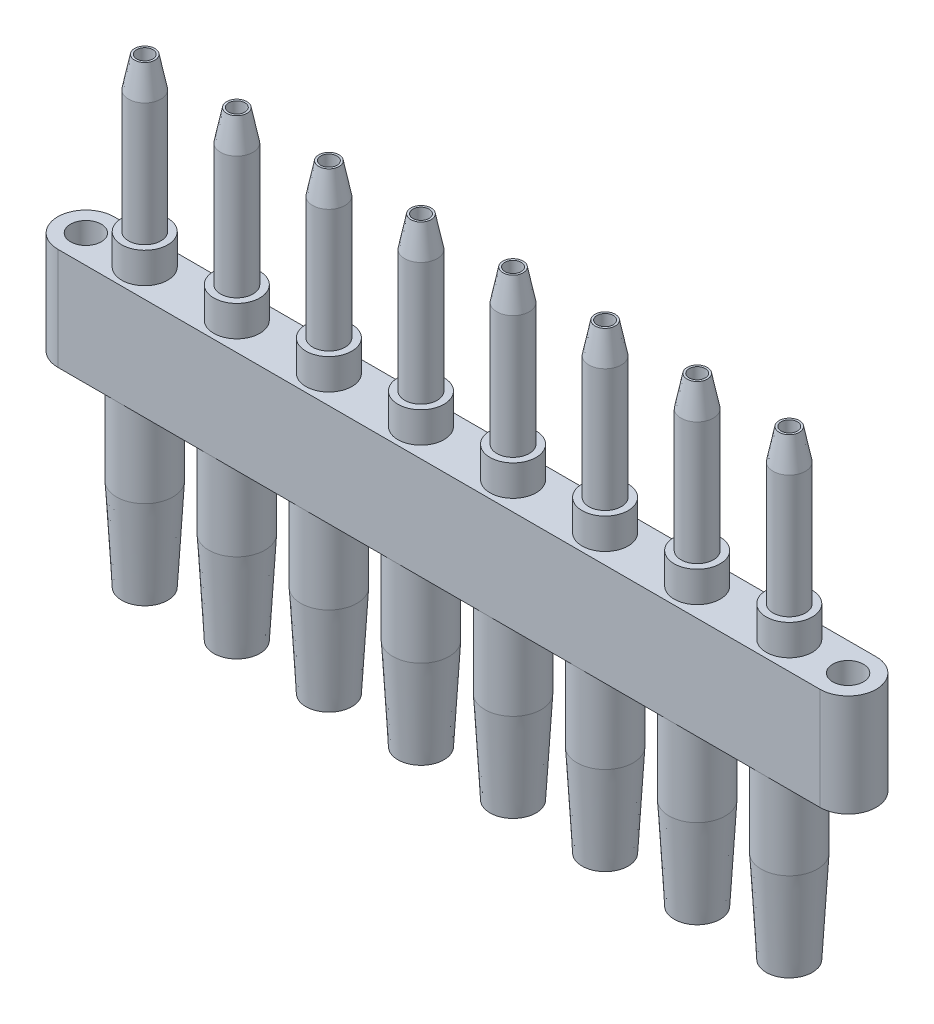
SolidWorks part; units mm, degrees
ref_plane "Front Plane" through (0, 0, 0) normal (0, 0, 1) x (1, 0, 0)
ref_plane "Top Plane" through (0, 0, 0) normal (0, 1, 0) x (1, 0, 0)
ref_plane "Right Plane" through (0, 0, 0) normal (1, 0, 0) x (0, 0, -1)
sketch "Sketch1" plane through (0, 0, 0) normal (0, 1, 0) x (1, 0, 0)
  line L0 (0, 0) -> (0, 22.2718) construction
  circle A0 centre (0, 0) radius 4.5 construction
  circle A1 centre (-4.5, 0) radius 2.75
  circle A2 centre (4.5, 0) radius 2.75
  circle A3 centre (13.5, 0) radius 2.75
  circle A4 centre (22.5, 0) radius 2.75
  circle A5 centre (31.5, 0) radius 2.75
  circle A6 centre (-13.5, 0) radius 2.75
  circle A7 centre (-22.5, 0) radius 2.75
  circle A8 centre (-31.5, 0) radius 2.75
  circle A11 centre (-31.5, 0) radius 0.7937
  circle A12 centre (-22.5, 0) radius 0.7937
  circle A13 centre (-13.5, 0) radius 0.7937
  circle A14 centre (-4.5, 0) radius 0.7937
  circle A15 centre (4.5, 0) radius 0.7937
  circle A16 centre (13.5, 0) radius 0.7937
  circle A17 centre (22.5, 0) radius 0.7937
  circle A18 centre (31.5, 0) radius 0.7937
  dimension "D5" = 5.5
  dimension "D6" = 8
  dimension "D7" = 1.5875
  dimension "D8" = 9
  dimension "D4" = 4
extrude "Boss-Extrude1" add sketch "Sketch1" against normal blind 8.1
ref_plane "Plane1" through (0, -8.1, 0) normal (0, -1, 0) x (1, 0, 0)
ref_axis "Axis2" through (-31.5, -8.1, 0) along (0, 1, 0)
sketch "Sketch7" plane through (0, 0, 0) normal (0, 0, 1) x (1, 0, 0)
  line L1 (-31.5, -11) -> (-31.5, -15.2529)
sketch "Sketch8" plane through (0, -8.1, 0) normal (0, -1, 0) x (1, 0, 0)
  line L0 (-31.5, 0.7938) -> (-31.5, 2.75)
  circle A0 centre (-31.5, 0) radius 0.7937 construction
  circle A1 centre (-31.5, 0) radius 2.75 construction
ref_plane "Plane2" through (-31.5, 0, 0) normal (1, 0, 0) x (0, 0, -1)
sketch "Sketch9" plane through (-31.5, 0, 0) normal (1, 0, 0) x (0, 0, -1)
  line L0 (0, -11) -> (0, -15.2529) construction
  line L1 (-6.8585, -8.1) -> (6.8585, -8.1) construction
  line L2 (-0.7938, -8.1) -> (-0.7937, -17.1)
  line L3 (-0.7938, -8.1) -> (-2.75, -8.1)
  line L4 (0, -15.2529) -> (0, -21) construction
  line L5 (-0.7937, -17.1) -> (-2.25, -17.1)
  line L6 (-2.75, -8.1) -> (-2.25, -17.1)
  circle A0 centre (0, -8.1) radius 0.7937 construction
  circle A1 centre (0, -8.1) radius 1.5875 construction
  circle A2 centre (0, -17.1) radius 2.25 construction
  circle A3 centre (0, -8.1) radius 2.75 construction
  dimension "D1" = 4.5
  dimension "D2" = 5.5
  dimension "D3" = 9
revolve "Revolve1" add sketch "Sketch9" angle 360 about L4
ref_axis "Axis3" through (45.6173, -8.1, 0) along (-1, 0, 0)
pattern_linear "LPattern4" count 8 spacing 9 along (1, 0, 0) of bodies 109
sketch "Sketch10" plane through (0, 0, 0) normal (0, 1, 0) x (1, 0, 0)
  line L0 (0, 0) -> (-8.0623, 0) construction
  line L1 (-37.25, 2.75) -> (-37.25, -2.75) construction
  line L2 (0, 0) -> (0, 13.1499) construction
  line L3 (-37.25, 0) -> (-40, 0) construction
  line L4 (37.25, -2.75) -> (-37.25, -2.75)
  line L5 (37.25, 2.75) -> (-37.25, 2.75)
  line L6 (37.25, 2.75) -> (37.25, -2.75) construction
  line L7 (37.25, 0) -> (40, 0) construction
  line L9 (45.6173, 0) -> (-45.6488, 0) construction
  circle A0 centre (-31.5, 0) radius 0.7937
  circle A1 centre (-22.5, 0) radius 0.7937
  arc A2 (-37.25, 2.75) -> (-37.25, -2.75) centre (-37.25, 0) ccw
  circle A3 centre (-37.25, 0) radius 1.5
  circle A4 centre (37.25, 0) radius 1.5
  arc A5 (37.25, 2.75) -> (37.25, -2.75) centre (37.25, 0) cw
  circle A8 centre (-22.5, 0) radius 2.75 construction
  circle A9 centre (-13.5, 0) radius 0.7937
  circle A10 centre (-13.5, 0) radius 2.75 construction
  circle A11 centre (-4.5, 0) radius 0.7937
  circle A12 centre (-4.5, 0) radius 2.75 construction
  circle A13 centre (4.5, 0) radius 0.7937
  circle A14 centre (-31.5, 0) radius 2.75 construction
  circle A15 centre (4.5, 0) radius 2.75 construction
  circle A16 centre (13.5, 0) radius 0.7937
  circle A17 centre (13.5, 0) radius 2.75 construction
  circle A18 centre (22.5, 0) radius 0.7937
  circle A19 centre (22.5, 0) radius 2.75 construction
  circle A20 centre (31.5, 0) radius 0.7937
  circle A21 centre (31.5, 0) radius 2.75 construction
  dimension "D1" = 8
  dimension "D2" = 3
extrude "Boss-Extrude2" add sketch "Sketch10" along normal blind 10
sketch "Sketch11" plane through (0, 10, 0) normal (0, 1, 0) x (1, 0, 0)
  circle A0 centre (-31.5, 0) radius 0.7937
  circle A1 centre (-31.5, 0) radius 0.0625
  circle A2 centre (-31.5, 0) radius 1.5875
  circle A3 centre (-22.5, 0) radius 0.7937
  circle A4 centre (-22.5, 0) radius 0.0625
  circle A5 centre (-22.5, 0) radius 1.5875
  circle A6 centre (-13.5, 0) radius 0.7937
  circle A7 centre (-13.5, 0) radius 0.0625
  circle A8 centre (-13.5, 0) radius 1.5875
  circle A9 centre (-4.5, 0) radius 0.7937
  circle A10 centre (-4.5, 0) radius 0.0625
  circle A11 centre (-4.5, 0) radius 1.5875
  circle A12 centre (4.5, 0) radius 0.7937
  circle A13 centre (4.5, 0) radius 0.0625
  circle A14 centre (4.5, 0) radius 1.5875
  circle A15 centre (13.5, 0) radius 0.7937
  circle A16 centre (13.5, 0) radius 0.0625
  circle A17 centre (13.5, 0) radius 1.5875
  circle A18 centre (22.5, 0) radius 0.7937
  circle A19 centre (22.5, 0) radius 0.0625
  circle A20 centre (22.5, 0) radius 1.5875
  circle A21 centre (31.5, 0) radius 0.7937
  circle A22 centre (31.5, 0) radius 0.0625
  circle A23 centre (31.5, 0) radius 1.5875
  circle M13 centre (-31.5, 0) radius 0.7937
  dimension "D1" = 8
extrude "Boss-Extrude3" add sketch "Sketch11" along normal blind 15 separate body contours A11 | A8 | A5 | A2 M13 | A14 | A17 | A20 | A23 region at (-33.0426, 10, 0) region at (-24.0426, 10, 0) region at (-15.0426, 10, 0) region at (-6.0426, 10, 0) region at (2.9574, 10, 0) region at (11.9574, 10, 0) region at (20.9574, 10, 0) region at (29.9574, 10, 0)
ref_plane "Plane6" through (0, 25, 0) normal (0, 1, 0) x (-1, 0, 0)
ref_axis "Axis6" through (-31.5, 25, 0) along (0, -1, 0)
sketch "Sketch18" plane through (0, 0, 0) normal (0, 0, 1) x (1, 0, 0)
  line L1 (-32.4922, 28) -> (-32.2937, 28)
  line L2 (-32.2937, 25) -> (-32.2937, 28)
  line L3 (-32.4922, 28) -> (-33.0875, 25)
  line L4 (-33.0875, 25) -> (-32.2937, 25)
revolve "Revolve3" add sketch "Sketch18" angle 360 about axis through (-31.5, 25, 0) along (0, -1, 0)
ref_axis "Axis7" through (-24.2462, 25, 0) along (1, 0, 0)
pattern_linear "LPattern6" count 8 spacing 9 along (1, 0, 0) of "Revolve3"
extrude "Boss-Extrude5" add sketch "Sketch10<2>" along normal blind 10 contours A14 A0 | A8 A1 | A10 A9 | A12 A11 | A15 A13 | A21 A19 A17 A15 A14 A12 A10 A8 | A17 A16 | A21 A20 | A19 region at (0, 0, 0)
sketch "Sketch10<2>" plane through (0, 0, 0) normal (0, 1, 0) x (1, 0, 0) same geometry as "Sketch10"
ref_plane "Plane7" through (0, 10, 0) normal (0, 1, 0) x (-1, 0, 0)
sketch "Sketch20" plane through (0, 10, 0) normal (0, 1, 0) x (-1, 0, 0)
  circle A0 centre (-31.5, 0) radius 2.25
  circle A1 centre (-31.5, 0) radius 0.7937
  circle A2 centre (-22.5, 0) radius 2.25
  circle A3 centre (-22.5, 0) radius 0.7937
  circle A4 centre (-13.5, 0) radius 2.25
  circle A5 centre (-13.5, 0) radius 0.7937
  circle A6 centre (-4.5, 0) radius 2.25
  circle A7 centre (-4.5, 0) radius 0.7937
  circle A8 centre (4.5, 0) radius 2.25
  circle A9 centre (4.5, 0) radius 0.7937
  circle A10 centre (13.5, 0) radius 2.25
  circle A11 centre (13.5, 0) radius 0.7937
  circle A12 centre (22.5, 0) radius 2.25
  circle A13 centre (22.5, 0) radius 0.7937
  circle A14 centre (31.5, 0) radius 2.25
  circle A15 centre (31.5, 0) radius 0.7937
  dimension "D1" = 8
extrude "Boss-Extrude6" add sketch "Sketch20" along normal blind 3
combine bodies "Combine1" operation type add bodies to combine 170 109
combine bodies "Combine2" operation type add bodies to combine 172 110 111 112 113 114 115 116
